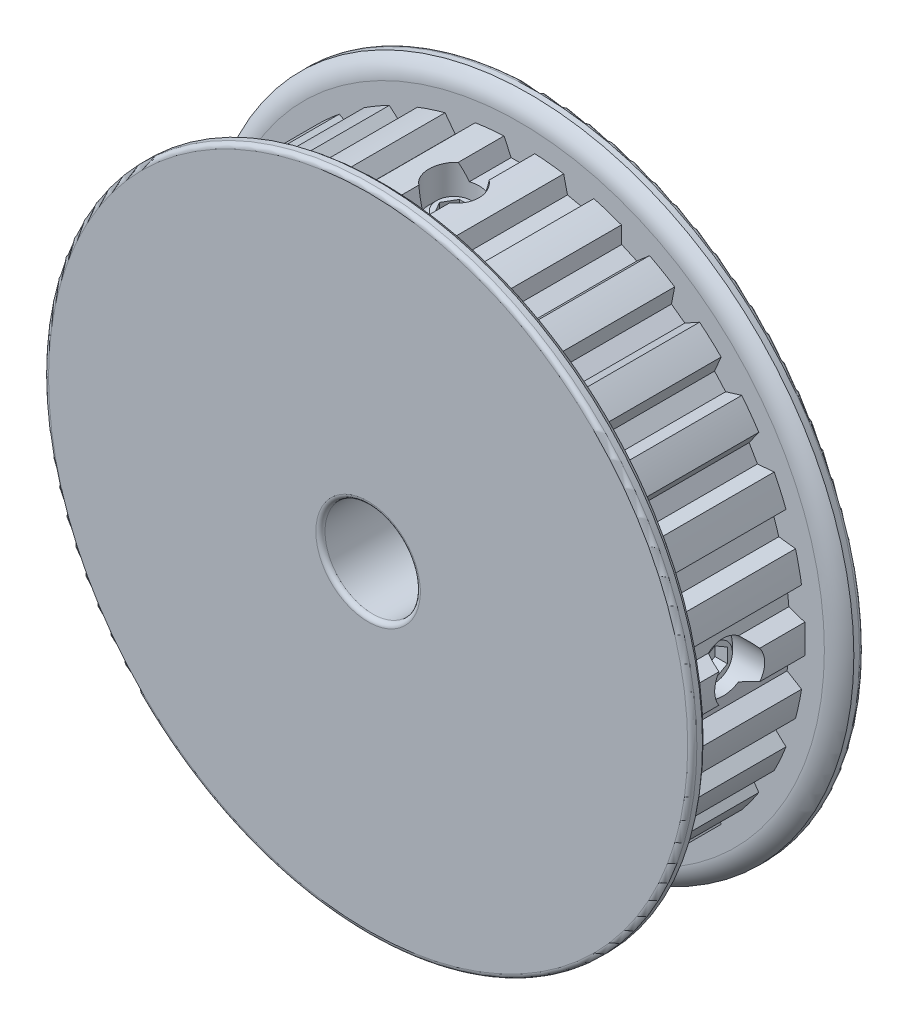
SolidWorks part; units mm, degrees
note: '?' marks a value the reader was unsure of.
ref_plane "Front Plane" through (0, 0, 0) normal (0, 0, 1) x (1, 0, 0)
ref_plane "Top Plane" through (0, 0, 0) normal (0, 1, 0) x (1, 0, 0)
ref_plane "Right Plane" through (0, 0, 0) normal (1, 0, 0) x (0, 0, -1)
sketch "Sketch1" plane through (0, 0, 0) normal (0, 0, 1) x (1, 0, 0)
  line L0 (-1.2827, 23.749) -> (-0.6905, 22.479)
  line L1 (-0.6905, 22.479) -> (0.6905, 22.479)
  line L2 (0.6905, 22.479) -> (1.2827, 23.749)
  line L3 (-1.2827, 23.749) -> (1.2827, 23.749)
  line L4 (0, 0) -> (0, 22.479) construction
  line L5 (0, 22.479) -> (0, 24.765) construction
  circle A0 centre (0, 0) radius 24.257 construction
  circle A1 centre (0, 0) radius 26.9875 construction
  circle A2 centre (0, 0) radius 23.7836 construction
  point P6 (0, 23.749)
  point P11 (0, 24.257)
  point P13 (0, 26.9875)
  point P14 (0, 23.7836)
  dimension "D1" = 1.016
  dimension "PD" = 48.514
  dimension "D2" = 0.508
  dimension "OD" = 53.975
  dimension "b" = 50
  dimension "bt" = 2.5654
  dimension "ht" = 1.27
  dimension "hs" = 2.286
sketch "Sketch2" plane through (0, 0, 0) normal (1, 0, 0) x (0, 0, -1)
  line L0 (-7.1501, 3.9688) -> (7.1501, 3.9688)
  line L3 (-7.1501, 3.9688) -> (-7.1501, 26.9875)
  line L4 (-7.1501, 26.9875) -> (-5.4483, 26.9875) construction
  line L5 (-5.4483, 26.9875) -> (-5.4483, 23.7836) construction
  line L6 (-5.4483, 23.7836) -> (5.4483, 23.7836)
  line L7 (5.4483, 23.7836) -> (5.4483, 26.9875) construction
  line L8 (5.4483, 26.9875) -> (7.1501, 26.9875) construction
  line L9 (7.1501, 26.9875) -> (7.1501, 3.9688)
  line L10 (-7.1501, 0) -> (7.1501, 0) construction
  line L13 (-7.1501, 26.9875) -> (-6.2992, 26.9875)
  line L14 (-5.4483, 25.3856) -> (-5.4483, 23.7836)
  line L15 (5.4483, 23.7836) -> (5.4483, 25.3856)
  line L16 (6.2992, 26.9875) -> (7.1501, 26.9875)
  arc A0 (-5.4483, 25.3856) -> (-6.2992, 26.9875) centre (-7.3817, 25.3856) ccw
  arc A1 (5.4483, 25.3856) -> (6.2992, 26.9875) centre (7.3817, 25.3856) cw
  point P12 (-5.4483, 25.3856)
  point P14 (-6.2992, 26.9875)
  point P20 (5.4483, 25.3856)
  point P21 (6.2992, 26.9875)
  point P25 (5.4483, 0)
  point P26 (-5.4483, 0)
  dimension "OA" = 14.3002
  dimension "Bore" = 7.9375
  dimension "Outside Width" = 14.3002
  dimension "Inside Width" = 10.8966
revolve "Revolve1" add sketch "Sketch2" angle 360 mid plane about L10
sketch "Sketch3" plane through (0, 0, 0) normal (0, 0, 1) x (1, 0, 0)
  line L0 (-0.6905, 22.479) -> (0.6905, 22.479) construction
  line L1 (0.6905, 22.479) -> (1.2827, 23.749) construction
  line L2 (-1.2827, 23.749) -> (-0.6905, 22.479) construction
  line L3 (-0.6905, 22.479) -> (0.6905, 22.479)
  line L4 (0.6905, 22.479) -> (1.2827, 23.749)
  line L5 (-1.2827, 23.749) -> (-0.6905, 22.479)
  circle A0 centre (0, 0) radius 23.7836 construction
  arc A1 (1.2827, 23.749) -> (-1.2827, 23.749) centre (0, 0) ccw
extrude "Cut-Extrude1" cut sketch "Sketch3" against normal up to vertex (5.4483 mm away) from vertex at 5.4483 starting at point (0, 23.7836, 5.4483)
pattern_circular "CirPattern1" count 30 over 360 about axis through (0, 0, 0) along (0, 0, 1) of "Cut-Extrude1"
fillet "Fillet1" radius 0.381 4 edges at (3.9688, 0, -7.1501) (26.9875, 0, -7.1501) (26.9875, 0, 7.1501) (3.9688, 0, 7.1501)
sketch "Sketch5" plane through (0, 0, 0) normal (0, 1, 0) x (1, 0, 0)
  line L1 (1.2827, 0) -> (-1.2827, 0) construction
  line L2 (1.2827, 5.4483) -> (1.2827, -5.4483) construction
  line L3 (-1.2827, 5.4483) -> (-1.2827, -5.4483) construction
  circle A0 centre (0, 0) radius 2.0828
extrude "Cut-Extrude2" cut sketch "Sketch5" along normal through all
sketch "Sketch6" plane through (0, 0, 0) normal (1, 0, 0) x (0, 0, -1)
  line L0 (0, 21.717) -> (0, 4.7308)
  line L1 (6.7691, 3.9688) -> (-6.7691, 3.9688) construction
  line L3 (2.0828, 22.479) -> (-2.0828, 22.479) construction
  line L4 (-1.965, 22.479) -> (-2.0828, 22.479) construction
  line L5 (2.0828, 22.479) -> (1.965, 22.479) construction
  line L6 (0, 21.717) -> (-1.458, 21.717)
  line L7 (-1.458, 21.717) -> (-2.0828, 21.0922)
  line L8 (-2.0828, 21.0922) -> (-2.0828, 5.3556)
  line L9 (-2.0828, 5.3556) -> (-1.458, 4.7307)
  line L10 (-1.458, 4.7307) -> (0, 4.7308)
  point P12 (0, 3.9688)
  point P19 (0, 22.479)
  dimension "D1" = 0.762
  dimension "D2" = 0.762
  dimension "D3" = 135
  dimension "D4" = 0.6248
revolve "Revolve2" add sketch "Sketch6" angle 360 about L0
sketch "Sketch7" plane through (0, 21.717, 0) normal (0, 1, 0) x (1, 0, 0)
  line L1 (1.2025, 0) -> (0.6013, 1.0414)
  line L2 (0.6013, 1.0414) -> (-0.6013, 1.0414)
  line L3 (-0.6013, 1.0414) -> (-1.2025, 0)
  line L4 (-1.2025, 0) -> (-0.6013, -1.0414)
  line L5 (-0.6013, -1.0414) -> (0.6013, -1.0414)
  line L6 (0.6013, -1.0414) -> (1.2025, 0)
  circle A0 centre (0, 0) radius 1.0414 construction
  dimension "D1" = 2.0828
extrude "Cut-Extrude3" cut sketch "Sketch7" against normal blind 1.0414
pattern_circular "CirPattern2" count 2 over 270 about axis through (0, 0, 0) along (0, 0, 1) of "Cut-Extrude2", "Revolve2", "Cut-Extrude3"
ref_axis "Center Axis 1" through (0, 0, -6.7691) along (0, 0, 1)?
ref_plane "Contact Plane 1" through (0, 0, 7.1501) normal (0, 0, 1) x (1, 0, 0)
ref_plane "Contact Plane 2" through (0, 0, -7.1501) normal (0, 0, -1) x (-1, 0, 0)
equation "\"D4@Sketch6\" = \"Set Screw Dia@Sketch5\" * .15"
equation "\"D1@Sketch7\" = \"Set Screw Dia@Sketch5\" / 2"
equation "\"D1@Cut-Extrude3\" = \"Set Screw Dia@Sketch5\" / 4"
